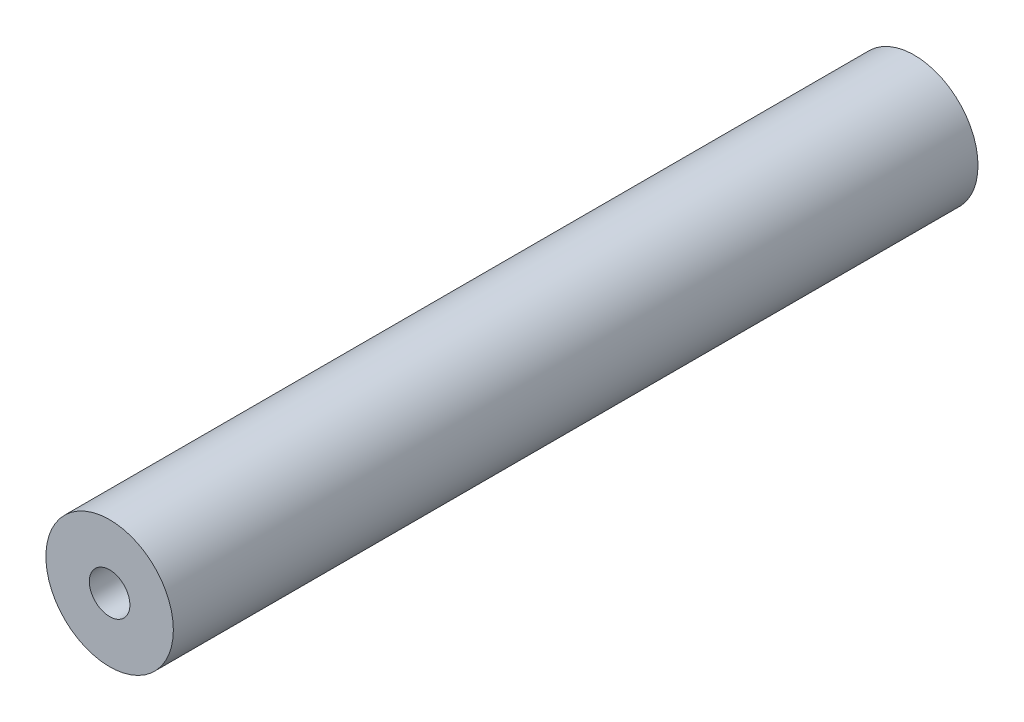
SolidWorks part; units mm, degrees
material "6061-T6 (SS)"
ref_plane "Front Plane" through (0, 0, 0) normal (0, 0, 1) x (1, 0, 0)
ref_plane "Top Plane" through (0, 0, 0) normal (0, 1, 0) x (1, 0, 0)
ref_plane "Right Plane" through (0, 0, 0) normal (1, 0, 0) x (0, 0, -1)
sketch "Sketch1" plane through (0, 0, 0) normal (0, 0, 1) x (1, 0, 0)
  circle A1 centre (0, 0) radius 6.35
  dimension "D2" = 12.7
extrude "Boss-Extrude1" add sketch "Sketch1" along normal mid plane 80.17 contours A1 region at (0, 0, 0)
hole_wizard "#10-32 Tapped Hole1" positions "3DSketch1" profile "Sketch2" tap size "#10-32" standard "ANSI Inch"
sketch3d "3DSketch1"
  line L0 (0, 0, 40.085) -> (0, 0, -40.085) construction
  point P0 (0, 0, -40.085)
  point P4 (0, 0, 40.085)
sketch "Sketch2" plane through (0, 0, -40.085) normal (1, 0, 0) x (0, 1, 0)
  line L0 (0, 0) -> (0, 13.2428)
  line L1 (0, 13.2428) -> (2.0193, 12.0294)
  line L2 (2.0193, 12.0294) -> (2.0193, 0)
  line L5 (2.0193, 0) -> (0, 0)
  line L10 (0, 13.2428) -> (-2.0193, 12.0294) construction
  line L11 (0, -6.35) -> (0, 107.95) construction
  dimension "Tap Drill Dia." = 4.0386
  dimension "Tap Drill Depth" = 12.0294
  dimension "Drill Angle" = 118
cosmetic thread "Hole Thread1" parameters "D1"=9.652, "D2"=4.826
cosmetic thread "Hole Thread2" parameters "D1"=9.652, "D2"=4.826
